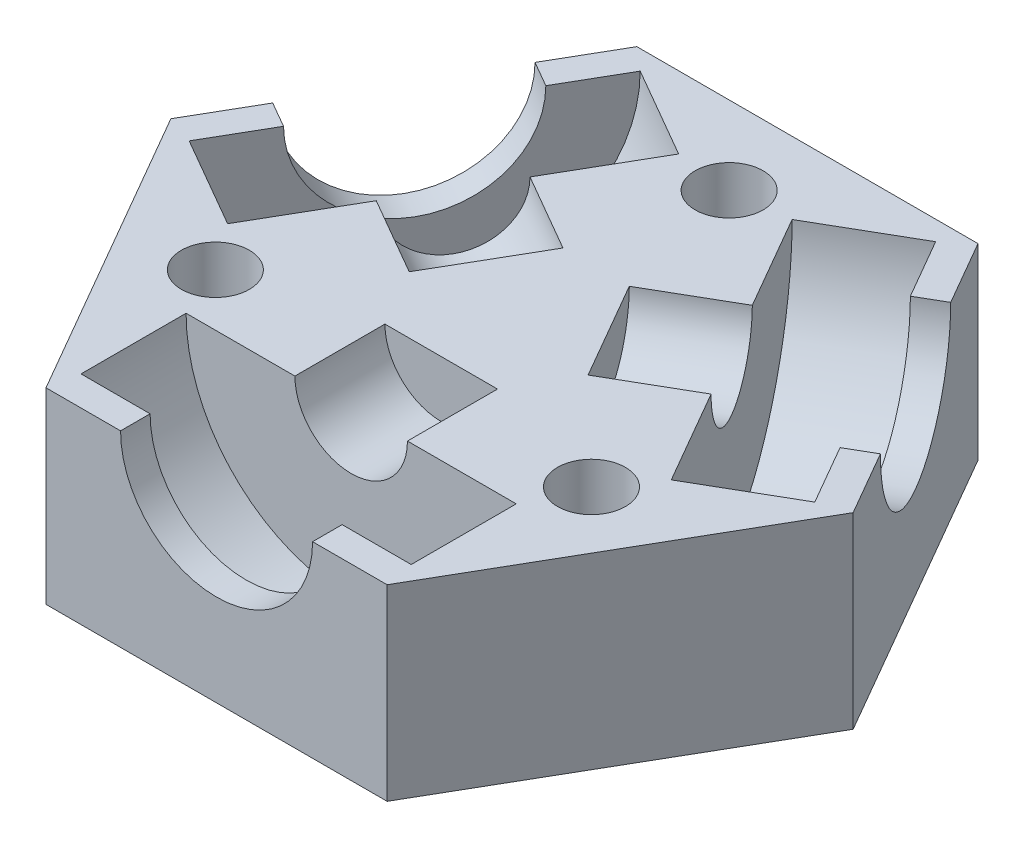
SolidWorks part; units mm, degrees
ref_plane "Front Plane" through (0, 0, 0) normal (0, 0, 1) x (1, 0, 0)
ref_plane "Top Plane" through (0, 0, 0) normal (0, 1, 0) x (1, 0, 0)
ref_plane "Right Plane" through (0, 0, 0) normal (1, 0, 0) x (0, 0, -1)
sketch "Sketch1" plane through (0, 0, 0) normal (0, 1, 0) x (1, 0, 0)
  line L1 (11.547, -20) -> (23.094, 0)
  line L2 (23.094, 0) -> (11.547, 20)
  line L3 (11.547, 20) -> (-11.547, 20)
  line L4 (-11.547, 20) -> (-23.094, 0)
  line L5 (-23.094, 0) -> (-11.547, -20)
  line L6 (-11.547, -20) -> (11.547, -20)
  circle A0 centre (0, 0) radius 20 construction
  point P1 (0, 0)
  dimension "D1" = 40
extrude "Boss-Extrude1" add sketch "Sketch1" along normal blind 12.7 contours L4 L5 L6 L1 L2 L3
sketch "Sketch5" plane through (0, 12.7, 0) normal (0, 1, 0) x (1, 0, 0)
  line L14 (0, -20) -> (0, -4.792)
  line L15 (-11.547, -20) -> (11.547, -20) construction
  line L16 (0, -4.792) -> (-3.81, -4.792)
  line L17 (-3.81, -4.792) -> (-3.81, -10.888)
  line L18 (-3.81, -10.888) -> (-11.176, -10.888)
  line L19 (-11.176, -10.888) -> (-11.176, -18)
  line L20 (-11.176, -18) -> (-6.5, -18)
  line L21 (-6.5, -18) -> (-6.5, -20)
  line L22 (-6.5, -20) -> (0, -20)
  dimension "D1" = 6.5
  dimension "D2" = 11.176
  dimension "D3" = 2
  dimension "D4" = 7.112
  dimension "D5" = 6.096
  dimension "D6" = 3.81
revolve "Cut-Revolve1" cut sketch "Sketch5" angle 360 about L14
ref_axis "Axis1" through (0, -0.635, 0) along (0, 1, 0)
pattern_circular "CirPattern1" count 3 over 360 about axis through (0, -0.635, 0) along (0, 1, 0) of "Cut-Revolve1"
sketch "Sketch7" plane through (0, 12.7, 0) normal (0, 1, 0) x (1, 0, 0)
  line L0 (11.547, 20) -> (-11.547, 20) construction
  line L1 (-23.094, 0) -> (-11.547, -20) construction
  line L2 (11.547, -20) -> (23.094, 0) construction
  circle A0 centre (0, 14.7) radius 2.3
  circle A1 centre (12.7306, -7.35) radius 2.3
  circle A2 centre (-12.7306, -7.35) radius 2.3
  point P11 (0, 0)
  dimension "D1" = 4.6
  dimension "D2" = 3
  dimension "D4" = 3
  dimension "D5" = 3
  dimension "D3" = 3
extrude "Cut-Extrude2" cut sketch "Sketch7" against normal blind 6.35
